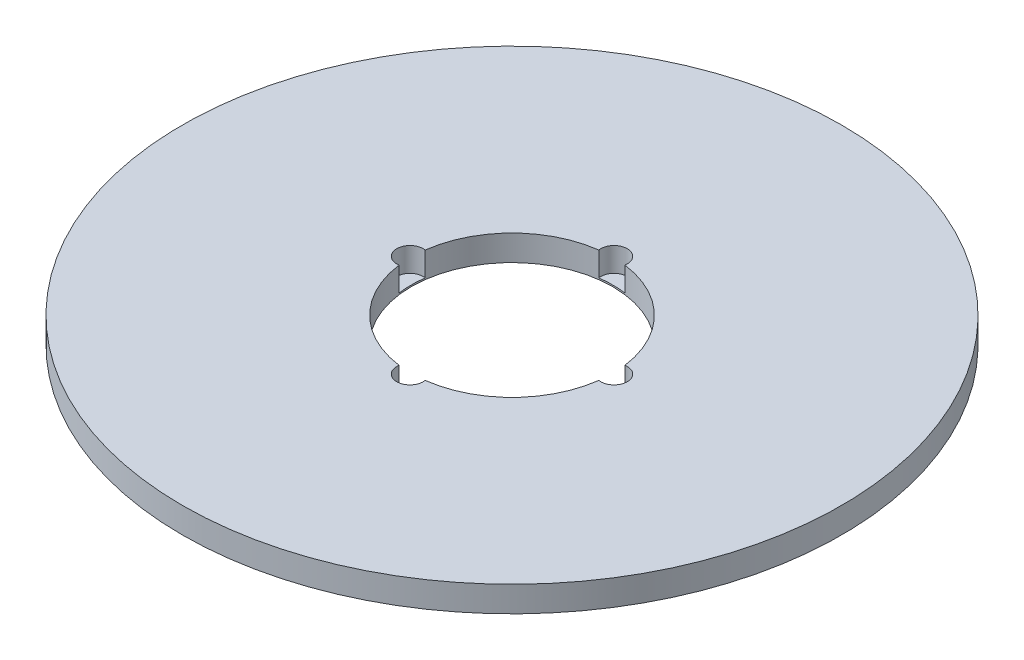
SolidWorks part; units mm, degrees
ref_plane "Front Plane" through (0, 0, 0) normal (0, 0, 1) x (1, 0, 0)
ref_plane "Top Plane" through (0, 0, 0) normal (0, 1, 0) x (1, 0, 0)
ref_plane "Right Plane" through (0, 0, 0) normal (1, 0, 0) x (0, 0, -1)
sketch "Sketch1" plane through (0, 0, 0) normal (0, 1, 0) x (1, 0, 0)
  circle A0 centre (0, 0) radius 90
  dimension "FLANGE_OD" = 180
extrude "Boss-Extrude1" add sketch "Sketch1" along normal blind 7
sketch "Sketch2" plane through (0, 0, 0) normal (0, 1, 0) x (1, 0, 0)
  circle A0 centre (0, 0) radius 27.5
  dimension "BORE_D" = 55
extrude "Cut-Extrude1" cut sketch "Sketch2" along normal through all
sketch "Sketch3" plane through (0, 7, 0) normal (0, 1, 0) x (1, 0, 0)
  circle A0 centre (0, 0) radius 27.8615 construction
  circle A1 centre (-27.8615, 0) radius 3.614
  dimension "BOLT_D" = 7.2281
  dimension "BOLT_PCD" = 55.723
extrude "Cut-Extrude2" cut sketch "Sketch3" against normal blind 6.5843
pattern_circular "CirPattern1" count 4 over 360 about axis through (0, 0, 0) along (0, 1, 0) of "Cut-Extrude2"
